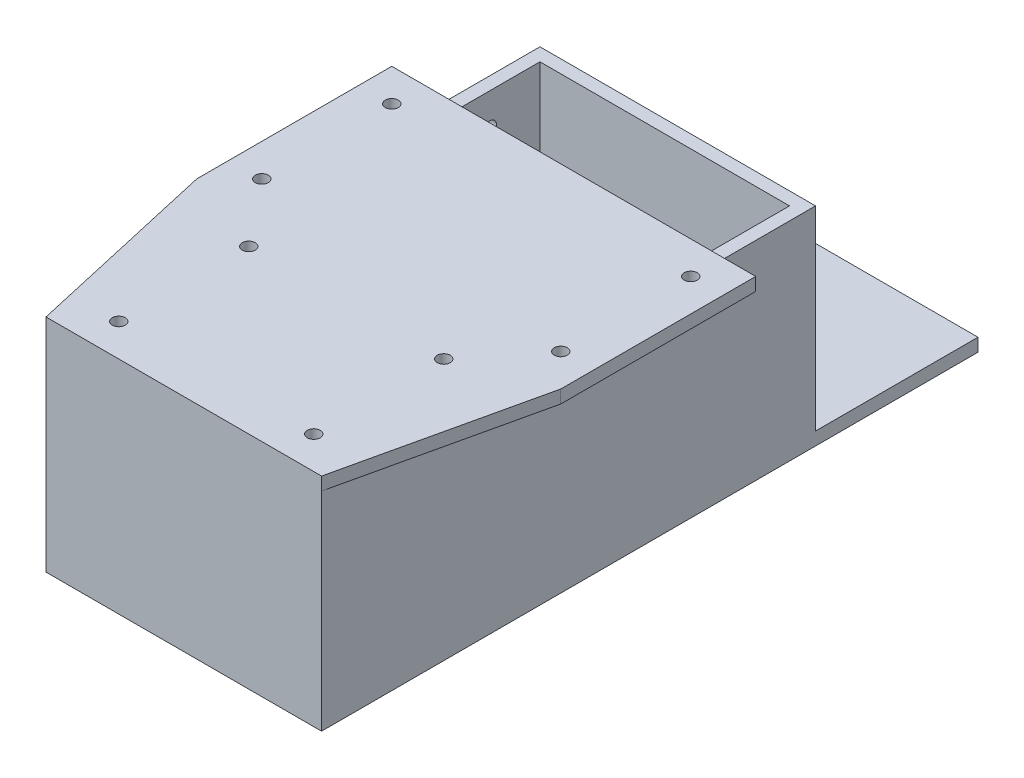
SolidWorks part; units mm, degrees
ref_plane "Front Plane" through (0, 0, 0) normal (0, 0, 1) x (1, 0, 0)
ref_plane "Top Plane" through (0, 0, 0) normal (0, 1, 0) x (1, 0, 0)
ref_plane "Right Plane" through (0, 0, 0) normal (1, 0, 0) x (0, 0, -1)
sketch "Sketch2" plane through (0, 0, 0) normal (0, 1, 0) x (1, 0, 0)
  line L0 (-2, -2) -> (-2, 74)
  line L1 (0, 0) -> (38.4, 0)
  line L2 (0, 0) -> (0, 72)
  line L3 (0, 72) -> (38.4, 72)
  line L4 (38.4, 0) -> (38.4, 72)
  line L5 (-2, 74) -> (40.4, 74)
  line L6 (40.4, -2) -> (40.4, 74)
  line L7 (-2, -2) -> (40.4, -2)
  dimension "D1" = 72
  dimension "D2" = 38.4
  dimension "D3" = 2
extrude "Boss-Extrude4" add sketch "Sketch2" along normal blind 32
sketch "Sketch1" plane through (0, 32, 0) normal (0, 1, 0) x (1, 0, 0)
  line L0 (19.2, 28) -> (19.2, -2) construction
  line L1 (-2, -2) -> (40.4, -2)
  line L2 (-2, -2) -> (-2, 28)
  line L3 (-2, 28) -> (40.4, 28)
  line L4 (40.4, -2) -> (40.4, 28)
  line L5 (-2, 13) -> (40.4, 13) construction
  line L6 (-2, -2) -> (40.4, -2) construction
  line L8 (40.4, -2) -> (40.4, 74) construction
  line L9 (-2, 74) -> (-2, -2) construction
  circle A0 centre (4.2, 3) radius 1
  circle A1 centre (34.2, 3) radius 1
  circle A2 centre (34.2, 23) radius 1
  circle A3 centre (4.2, 23) radius 1
  dimension "D3" = 2
  dimension "D1" = 30
  dimension "D2" = 20
  dimension "D4" = 30
extrude "Boss-Extrude1" add sketch "Sketch1" along normal blind 2
sketch "Sketch4" plane through (0, 32, 0) normal (0, 1, 0) x (1, 0, 0)
  line L0 (-8.8, 43) -> (47.2, 43) construction
  line L1 (47.2, 28) -> (-8.8, 28)
  line L2 (47.2, 28) -> (47.2, 58)
  line L3 (47.2, 58) -> (-8.8, 58)
  line L4 (-8.8, 28) -> (-8.8, 58)
  line L5 (19.2, 58) -> (19.2, 28) construction
  line L6 (40.4, 28) -> (-2, 28) construction
  circle A0 centre (-3.8, 33) radius 1
  circle A1 centre (-3.8, 53) radius 1
  circle A2 centre (42.2, 53) radius 1
  circle A3 centre (42.2, 33) radius 1
  dimension "D1" = 2
  dimension "D2" = 20
  dimension "D3" = 46
  dimension "D4" = 30
  dimension "D5" = 56
extrude "Boss-Extrude5" add sketch "Sketch4" along normal blind 2
sketch "Sketch5" plane through (-2, 0, 0) normal (-1, 0, 0) x (0, 0, 1)
  line L0 (2, 34) -> (2, 0) construction
  line L1 (-74, 32) -> (2, 32)
  line L2 (-74, 32) -> (-74, 0)
  line L3 (-74, 0) -> (2, 0)
  line L4 (2, 32) -> (2, 0)
  line L5 (-74, 0) -> (2, 0) construction
  line L6 (2, 16) -> (-74, 16) construction
  line L7 (-36, 32) -> (-36, 0) construction
  circle A0 centre (-7.7, 27) radius 1
  circle A1 centre (-7.7, 5) radius 1
  circle A2 centre (-64.3, 5) radius 1
  circle A3 centre (-64.3, 27) radius 1
  dimension "D1" = 2
  dimension "D2" = 56.6
  dimension "D3" = 22
extrude "Cut-Extrude1" cut sketch "Sketch5" against normal blind 2 contours A1 | A0 | A3 | A2 region at (-2, 27, -7.7) region at (-2, 5, -7.7) region at (-2, 5, -64.3) region at (-2, 27, -64.3)
sketch "Sketch9" plane through (0, 0, 0) normal (1, 0, 0) x (0, 0, -1)
  line L0 (36, 0) -> (36, 32) construction
  line L1 (72, 0) -> (0, 0) construction
  line L2 (58, 32) -> (0, 32) construction
  line L3 (56, 0) -> (56, 1)
  line L4 (56, 0) -> (16, 0)
  line L5 (36, 0) -> (36, 1)
  line L6 (56, 1) -> (16, 1)
  line L7 (16, 0) -> (16, 1)
  dimension "D1" = 1
  dimension "D2" = 20
revolve "Revolve1" add sketch "Sketch9" angle 360 about L6 region at (0, 0.5, -46) region at (0, 0.5, -26)
ref_plane "Plane1" through (19.2, 0, 0) normal (1, 0, 0) x (0, 0, -1)
mirror "Mirror1" about plane through (19.2, 0, 0) normal (1, 0, 0) of "Revolve1"
sketch "Sketch11" plane through (0, 0, -74) normal (0, 0, -1) x (-1, 0, 0)
  line L0 (-40.4, 32) -> (-40.4, 0) construction
  line L1 (2, 0) -> (-40.4, 0)
  line L2 (2, 0) -> (2, 2)
  line L3 (2, 2) -> (-40.4, 2)
  line L4 (-40.4, 0) -> (-40.4, 2)
  line L5 (-19.2, 0) -> (-19.2, -3)
  line L6 (-14.95, -3) -> (-23.45, -3)
  line L7 (-23.45, -3) -> (-23.45, 0)
  line L8 (-23.45, 0) -> (-14.95, 0)
  line L9 (-14.95, -3) -> (-14.95, 0)
  line M5 (-40.4, 0) -> (2, 0)
  line M6 (2, 0) -> (2, 32)
  line M8 (-40.4, 32) -> (-40.4, 0)
  dimension "D1" = 2
  dimension "D2" = 8.5
  dimension "D3" = 3
extrude "Boss-Extrude7" add sketch "Sketch11" along normal blind 25 and the other way up to surface (2 mm away) contours L3 L1 M6 M8 M5 | L7 L6 L5 L1 | L6 L9 L1 L5 region at (19.2, 1, -74) region at (17.075, -1.5, -74) region at (21.325, -1.5, -74) other way up to face at (19.2, 16, -72)
sketch "Sketch12" plane through (0, 2, 0) normal (0, 1, 0) x (1, 0, 0)
  line L0 (40.4, 86.5) -> (-2, 86.5) construction
  line L1 (40.4, 99) -> (40.4, 74) construction
  line L2 (-2, 99) -> (-2, 74) construction
  line L3 (19.2, 99) -> (19.2, 74) construction
  line L4 (-2, 99) -> (40.4, 99) construction
  line L5 (-2, 74) -> (40.4, 74) construction
  circle A0 centre (19.2, 86.5) radius 4
  dimension "D1" = 8
extrude "Cut-Extrude2" cut sketch "Sketch12" against normal blind 25
chamfer "Chamfer1" distance 1 angle 45 2 edges at (14.95, -3, -85.5) (23.45, -3, -85.5)
sketch "Sketch13" plane through (0, 34, 0) normal (0, 1, 0) x (1, 0, 0)
  line L0 (40.4, -2) -> (47.2, 28)
  line L1 (47.2, 28) -> (40.4, 28)
  line L2 (40.4, 28) -> (40.4, -2)
  line L3 (-8.8, 28) -> (-2, 28)
  line L4 (-2, 28) -> (-2, -2)
  line L5 (-2, -2) -> (-8.8, 28)
extrude "Boss-Extrude8" add sketch "Sketch13" against normal up to surface (2 mm away) up to face at (19.2, 32, -29)
